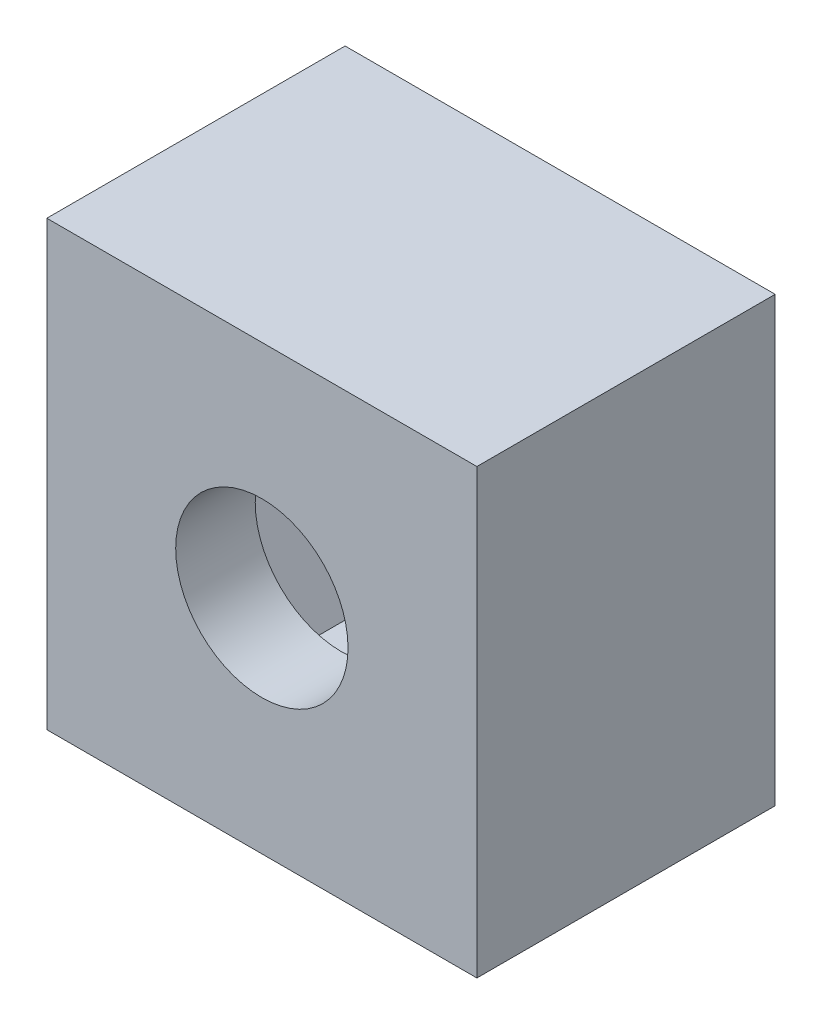
SolidWorks part; units mm, degrees
ref_plane "Front Plane" through (0, 0, 0) normal (0, 0, 1) x (1, 0, 0)
ref_plane "Top Plane" through (0, 0, 0) normal (0, 1, 0) x (1, 0, 0)
ref_plane "Right Plane" through (0, 0, 0) normal (1, 0, 0) x (0, 0, -1)
sketch "Sketch1" plane through (0, 0, 0) normal (0, 0, 1) x (1, 0, 0)
  line L1 (6.2546, 0) -> (3.1273, 5.4167)
  line L2 (3.1273, 5.4167) -> (-3.1273, 5.4167)
  line L3 (-3.1273, 5.4167) -> (-6.2546, 0)
  line L4 (-6.2546, 0) -> (-3.1273, -5.4167)
  line L5 (-3.1273, -5.4167) -> (3.1273, -5.4167)
  line L6 (3.1273, -5.4167) -> (6.2546, 0)
  line L7 (-8.1103, -8.3534) -> (8.1103, -8.3534)
  line L8 (-8.1103, -8.3534) -> (-8.1103, 8.3534)
  line L9 (-8.1103, 8.3534) -> (8.1103, 8.3534)
  line L10 (8.1103, -8.3534) -> (8.1103, 8.3534)
  line L11 (-8.1103, -8.3534) -> (8.1103, 8.3534) construction
  line L12 (-8.1103, 8.3534) -> (8.1103, -8.3534) construction
  circle A0 centre (0, 0) radius 5.4167 construction
  circle A1 centre (0, 0) radius 3.25
  dimension "D1" = 6.5
extrude "Boss-Extrude1" add sketch "Sketch1" along normal blind 5.25 contours L7 L10 L9 L8 L6 L5 L4 L3 L2 L1 region at (-7.8774, 0, 0)
sketch "Sketch2" plane through (0, 0, 5.25) normal (0, 0, 1) x (1, 0, 0)
  line L1 (-8.1103, 8.3534) -> (8.1103, 8.3534)
  line L2 (-8.1103, 8.3534) -> (-8.1103, -8.3534)
  line L3 (-8.1103, -8.3534) -> (8.1103, -8.3534)
  line L4 (8.1103, 8.3534) -> (8.1103, -8.3534)
  circle A0 centre (0, 0) radius 3.25
  dimension "D1" = 6.5
extrude "Boss-Extrude2" add sketch "Sketch2" along normal blind 3
extrude "Boss-Extrude3" add sketch "Sketch1<3>" against normal blind 3 contours L5 L6 L1 L2 L3 L4 A1 | L7 L10 L9 L8 L6 L5 L4 L3 L2 L1 region at (4.5477, -2.6256, 0) region at (-7.8774, 0, 0)
sketch "Sketch1<3>" plane through (0, 0, 0) normal (0, 0, 1) x (1, 0, 0) same geometry as "Sketch1"
